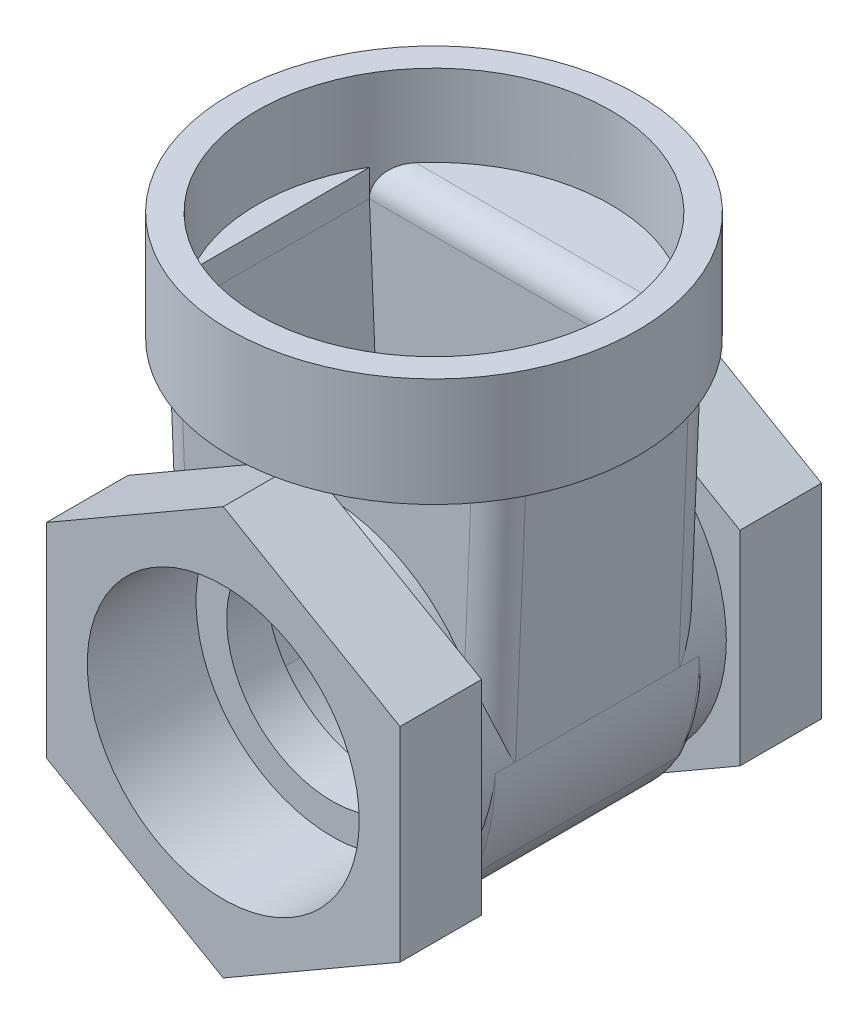
SolidWorks part; units mm, degrees
material "Latón"
ref_plane "Alzado" through (0, 0, 0) normal (0, 0, 1) x (1, 0, 0)
ref_plane "Planta" through (0, 0, 0) normal (0, 1, 0) x (1, 0, 0)
ref_plane "Vista lateral" through (0, 0, 0) normal (1, 0, 0) x (0, 0, -1)
sketch "Croquis1" plane through (0, 0, 0) normal (1, 0, 0) x (0, 0, -1)
  line L0 (0, 0) -> (24.6062, 0) construction
  line L1 (0, 0) -> (0, -19.05) construction
  line L2 (0, -19.05) -> (0, -15.875)
  line L3 (0, -15.875) -> (12.7, -15.875)
  line L4 (12.7, -15.875) -> (12.7, -12.3031)
  line L5 (12.7, -12.3031) -> (18.2563, -12.3031)
  line L6 (18.2563, -12.3031) -> (18.2563, -17.0656)
  line L7 (18.2563, -17.0656) -> (19.8438, -17.0656)
  line L8 (19.8438, -17.0656) -> (19.8438, -18.6531)
  line L9 (19.8438, -18.6531) -> (24.6062, -18.6531)
  line L10 (0, -19.05) -> (24.6062, -19.05)
  line L11 (24.6062, -19.05) -> (24.6062, -18.6531)
  dimension "D1" = 24.6062
  dimension "D2" = 19.05
  dimension "D3" = 3.175
  dimension "D4" = 12.7
  dimension "D5" = 24.6062
  dimension "D6" = 5.5562
  dimension "D7" = 4.7625
  dimension "D8" = 1.5875
  dimension "D9" = 1.5875
  dimension "D10" = 4.7625
  dimension "D11" = 24.6062
revolve "Revolución1" add sketch "Croquis1" angle 360 about L0
sketch "Croquis4" plane through (0, 0, 0) normal (0, 0, 1) x (1, 0, 0)
  circle A0 centre (0, 0) radius 15.875
curve "Hélice/Espiral2" pitch 2.3813 height 11.9062 turns 5
sketch "Croquis5" plane through (0, 0, 0) normal (0, 1, 0) x (1, 0, 0)
  line L0 (15.875, 0) -> (15.875, 1.1807)
  line L1 (15.875, 1.1807) -> (14.2875, 0)
  line L2 (-19.05, 0) -> (19.05, 0) construction
  line L3 (14.2875, 0) -> (15.875, -1.1807)
  line L4 (15.875, -1.1807) -> (15.875, 0)
  dimension "D1" = 1.5875
  dimension "D2" = 1.1807
sketch "Croquis6" plane through (0, 0, 0) normal (0, 0, 1) x (1, 0, 0)
  circle A0 centre (0, 0) radius 19.05
sketch "Croquis7" plane through (0, 0, -24.6062) normal (0, 0, -1) x (-1, 0, 0)
  line L0 (0, -18.6531) -> (0, -21.0344) construction
  line L1 (-19.05, 0) -> (-16.6687, 0) construction
  line L2 (19.05, 0) -> (16.6687, 0) construction
  line L3 (-19.05, 0) -> (-19.05, 28.575) construction
  line L4 (-19.05, 0) -> (-20.2406, 28.575)
  line L5 (-16.6687, 0) -> (-17.8594, 28.575)
  line L6 (16.6687, 0) -> (16.6687, 28.575) construction
  line L7 (16.6687, 0) -> (17.8594, 28.575)
  line L8 (19.05, 0) -> (20.2406, 28.575)
  line L9 (-20.2406, 28.575) -> (-17.8594, 28.575)
  line L10 (17.8594, 28.575) -> (20.2406, 28.575)
  line L11 (0, -1.9844) -> (-16.5064, -11.4944) construction
  line L12 (0, -1.9844) -> (16.4891, -11.5243) construction
  line L13 (-19.05, -1.9671) -> (19.05, -2.0016) construction
  arc A0 (-16.5064, -11.4944) -> (16.4891, -11.5243) centre (0, -1.9844) ccw
  arc A1 (19.05, 0) -> (16.4891, -11.5243) centre (-8.1613, 0) cw
  circle A2 centre (0, 0) radius 18.6531 construction
  circle A3 centre (0, 0) radius 19.05 construction
  arc A4 (-19.05, 0) -> (-16.5064, -11.4944) centre (8.1933, 0) ccw
  arc A5 (-14.4431, -10.3057) -> (14.428, -10.3318) centre (0, -1.9844) ccw
  arc A6 (-16.6687, 0) -> (-14.4431, -10.3057) centre (14.2738, 1.2893) ccw
  arc A7 (16.6687, 0) -> (14.428, -10.3318) centre (-14.202, 1.2863) cw
  dimension "D1" = 2.3813
  dimension "D12" = 30
  dimension "D2" = 2.3813
  dimension "D3" = 2.3813
  dimension "D4" = 1.1906
  dimension "D5" = 28.575
  dimension "D6" = 28.575
  dimension "D7" = 28.575
  dimension "D8" = 28.575
  dimension "D9" = 1.1906
  dimension "D10" = 28.575
  dimension "D11" = 28.575
  dimension "D13" = 30
extrude "Saliente-Extruir1" add sketch "Croquis7" against normal blind 12.7
sketch "Croquis8" plane through (0, 0, 0) normal (1, 0, 0) x (0, 0, -1)
  line L0 (18.2563, -17.0656) -> (16.6688, 17.0656)
  line L2 (18.2563, -17.0656) -> (18.2563, -6.99) construction
  line L4 (16.6688, 17.0656) -> (18.2563, 17.0656)
  line L5 (18.2563, 3.0277) -> (18.2563, 17.0656) construction
  line L6 (18.2563, 17.0656) -> (18.2563, -17.0656)
  dimension "D1" = 1.5875
extrude "Cortar-Extruir2" cut sketch "Croquis8" against normal blind 19.05 and the other way blind 19.05
sketch "Croquis9" plane through (0, 0, -24.6062) normal (0, 0, -1) x (-1, 0, 0)
  line L0 (16.9896, 7.7002) -> (16.6687, 0) construction
  line L1 (-16.6687, 0) -> (-16.9896, 7.7002) construction
  line L2 (16.9896, 7.7002) -> (16.6687, 0)
  line L3 (-16.6687, 0) -> (-16.9896, 7.7002)
  line L6 (-17.0249, 8.5473) -> (-17.8594, 28.575)
  line L7 (-17.8594, 28.575) -> (-20.2406, 28.575)
  line L8 (-20.2406, 28.575) -> (-19.05, 0)
  line L9 (19.05, 0) -> (20.2406, 28.575)
  line L10 (20.2406, 28.575) -> (17.8594, 28.575)
  line L11 (17.8594, 28.575) -> (17.0249, 8.5473)
  line L12 (-17.0249, 8.5473) -> (-17.8594, 28.575)
  line L13 (-17.8594, 28.575) -> (-20.2406, 28.575)
  line L14 (-20.2406, 28.575) -> (-19.05, 0)
  line L15 (19.05, 0) -> (20.2406, 28.575)
  line L16 (20.2406, 28.575) -> (17.8594, 28.575)
  line L17 (17.8594, 28.575) -> (17.0249, 8.5473)
  arc A0 (-14.4431, -10.3057) -> (14.428, -10.3318) centre (0, -1.9844) ccw construction
  arc A1 (-14.4431, -10.3057) -> (14.428, -10.3318) centre (0, -1.9844) ccw
  arc A2 (14.428, -10.3318) -> (16.6687, 0) centre (-14.202, 1.2863) ccw construction
  arc A3 (16.9896, 7.7002) -> (-16.9896, 7.7002) centre (0, 0) ccw construction
  arc A4 (17.0249, 8.5473) -> (-17.0249, 8.5473) centre (0, 0) ccw
  arc A5 (-19.05, 0) -> (-16.5064, -11.4944) centre (8.1933, 0) ccw
  arc A6 (-16.5064, -11.4944) -> (16.4891, -11.5243) centre (0, -1.9844) ccw
  arc A7 (16.4891, -11.5243) -> (19.05, 0) centre (-8.1613, 0) ccw
  arc A8 (17.0249, 8.5473) -> (-17.0249, 8.5473) centre (0, 0) ccw
  arc A9 (-19.05, 0) -> (-16.5064, -11.4944) centre (8.1933, 0) ccw
  arc A10 (-16.5064, -11.4944) -> (16.4891, -11.5243) centre (0, -1.9844) ccw
  arc A11 (16.4891, -11.5243) -> (19.05, 0) centre (-8.1613, 0) ccw
  arc A12 (-16.6687, 0) -> (-14.4431, -10.3057) centre (14.2738, 1.2893) ccw construction
  arc A13 (14.428, -10.3318) -> (16.6687, 0) centre (-14.202, 1.2863) ccw
  arc A14 (16.9896, 7.7002) -> (-16.9896, 7.7002) centre (0, 0) ccw
  arc A15 (-16.6687, 0) -> (-14.4431, -10.3057) centre (14.2738, 1.2893) ccw
  dimension "D1" = 0
extrude "Saliente-Extruir2" add sketch "Croquis9" against normal blind 9.525
sketch "Croquis10" plane through (0, 0, -24.6062) normal (0, 0, -1) x (-1, 0, 0)
  line L0 (-17.0249, 8.5473) -> (-16.7949, 3.0277)
  line L1 (-16.6687, 0) -> (-16.9896, 7.7002) construction
  line L2 (17.0249, 8.5473) -> (16.7949, 3.0277)
  arc A0 (16.7949, 3.0277) -> (-16.7949, 3.0277) centre (0, 0) ccw construction
  arc A1 (16.7949, 3.0277) -> (-16.7949, 3.0277) centre (0, 0) ccw
  arc A2 (17.0249, 8.5473) -> (-17.0249, 8.5473) centre (0, 0) ccw construction
  arc A3 (17.0249, 8.5473) -> (-17.0249, 8.5473) centre (0, 0) ccw
extrude "Cortar-Extruir3" cut sketch "Croquis10" against normal blind 9.525
sketch "Croquis11" plane through (0, 0, -11.9062) normal (0, 0, 1) x (1, 0, 0)
  line L1 (-17.8594, 28.575) -> (17.8594, 28.575)
  line L3 (17.8594, 28.575) -> (20.2406, 28.575) construction
  line L4 (20.2406, 28.575) -> (19.05, 0) construction
  line L5 (-20.2406, 28.575) -> (-17.8594, 28.575) construction
  line L6 (-19.05, 0) -> (-20.2406, 28.575) construction
  line L7 (17.8594, 28.575) -> (20.2406, 28.575)
  line L8 (20.2406, 28.575) -> (19.05, 0)
  line L9 (-20.2406, 28.575) -> (-17.8594, 28.575)
  line L10 (-19.05, 0) -> (-20.2406, 28.575)
  line L11 (16.7949, 3.0277) -> (19.05, 0)
  line L12 (-16.7949, 3.0277) -> (-19.05, 0)
  arc A0 (16.7949, 3.0277) -> (-16.7949, 3.0277) centre (0, 0) ccw construction
  arc A1 (16.7949, 3.0277) -> (-16.7949, 3.0277) centre (0, 0) ccw
extrude "Saliente-Extruir3" add sketch "Croquis11" against normal blind 2.3813
sketch "Croquis12" plane through (0, 0, 0) normal (0, 0, 1) x (1, 0, 0)
  line L0 (0, 0) -> (-20.6375, 0) construction
  line L1 (-20.6375, 0) -> (-20.6375, 11.9151)
  line L2 (-20.6375, 11.9151) -> (0, 0) construction
  line L3 (-20.6375, 0) -> (-20.6375, -11.9151)
  line L4 (-10.3187, 17.8726) -> (-20.6375, 11.9151)
  line L5 (-10.3187, 17.8726) -> (0, 23.8301)
  line L6 (10.3187, 17.8726) -> (0, 23.8301)
  line L7 (10.3187, 17.8726) -> (20.6375, 11.9151)
  line L8 (20.6375, 0) -> (20.6375, 11.9151)
  line L9 (20.6375, 0) -> (20.6375, -11.9151)
  line L10 (10.3187, -17.8726) -> (20.6375, -11.9151)
  line L11 (10.3187, -17.8726) -> (0, -23.8301)
  line L12 (-10.3188, -17.8726) -> (0, -23.8301)
  line L13 (-10.3188, -17.8726) -> (-20.6375, -11.9151)
  circle A0 centre (0, 0) radius 19.05
  point P23 (0, 0)
  dimension "D1" = 20.6375
  dimension "D2" = 30
  dimension "D3" = 6
extrude "Saliente-Extruir4" add sketch "Croquis12" against normal blind 9.525
ref_plane "Plano1" through (0, 0, -24.6062) normal (0, 0, -1) x (-1, 0, 0)
mirror "Simetría1" about plane through (0, 0, -24.6062) normal (0, 0, -1) of "Saliente-Extruir4", "Saliente-Extruir3", "Cortar-Extruir3", "Saliente-Extruir2", "Cortar-Extruir2", "Saliente-Extruir1", "Revolución1"
sketch "Croquis13" plane through (0, 28.575, 0) normal (0, 1, 0) x (1, 0, 0)
  line L0 (-20.2406, 37.3062) -> (20.2406, 11.9062) construction
  line L1 (-20.2406, 11.9062) -> (20.2406, 37.3062) construction
  line L4 (-17.8594, 14.2875) -> (17.8594, 14.2875)
  line L6 (-17.8594, 14.2875) -> (-17.8594, 34.925)
  line L7 (-17.8594, 34.925) -> (17.8594, 34.925)
  line L9 (17.8594, 14.2875) -> (17.8594, 34.925)
  circle A0 centre (0, 24.6062) radius 23.8125
  dimension "D1" = 47.625
extrude "Saliente-Extruir6" add sketch "Croquis13" along normal blind 12.7
sketch "Croquis14" plane through (0, 41.275, 0) normal (0, 1, 0) x (1, 0, 0)
  circle A0 centre (0, 24.6062) radius 20.6375
  dimension "D1" = 41.275
extrude "Cortar-Extruir4" cut sketch "Croquis14" against normal blind 9.525
fillet "Redondeo1" radius 3.175 4 edges at (-19.6453, 14.2875, -11.9062) (-19.6453, 14.2875, -37.3062) (19.6453, 14.2875, -37.3062) (19.6453, 14.2875, -11.9062)
fillet "Redondeo2" radius 0.7937 6 edges at (18.4065, -5.8862, -11.9062) (0.0173, -21.0344, -11.9062) (-18.4021, -5.9027, -11.9062) (18.4065, -5.8862, -37.3062) (0.0173, -21.0344, -37.3062) (-18.4021, -5.9027, -37.3062)
fillet "Redondeo3" radius 3.175 2 edges at (0, 31.75, -14.2875) (0, 31.75, -34.925)
